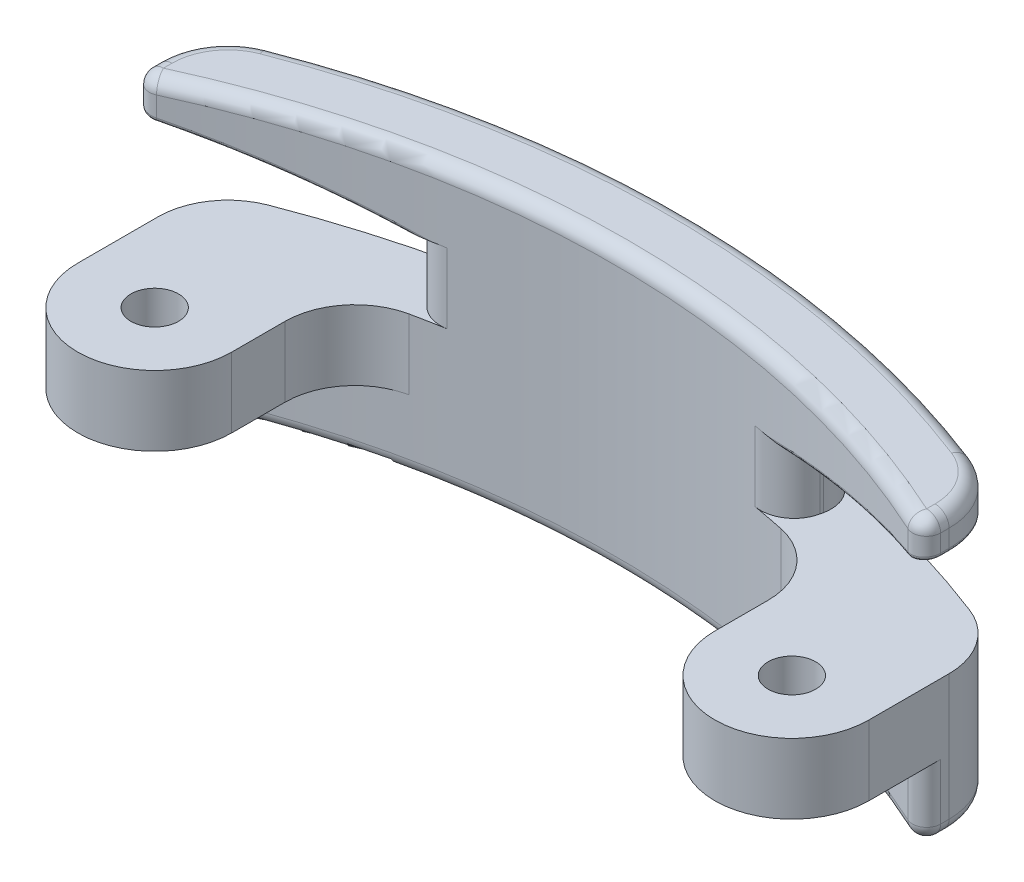
SolidWorks part; units mm, degrees
ref_plane "Front Plane" through (0, 0, 0) normal (0, 0, 1) x (1, 0, 0)
ref_plane "Top Plane" through (0, 0, 0) normal (0, 1, 0) x (1, 0, 0)
ref_plane "Right Plane" through (0, 0, 0) normal (1, 0, 0) x (0, 0, -1)
sketch "Sketch1" plane through (0, 0, 0) normal (0, 1, 0) x (1, 0, 0)
  line L0 (0, 0) -> (45.5, 0) construction
  line L1 (0, -54.3) -> (45.5, -54.3) construction
  line L2 (45.5, -54.3) -> (45.5, 0) construction
  line L3 (0, -54.3) -> (0, 0) construction
  line L4 (5.5, 0) -> (5.5, 3.7957)
  line L5 (40, 0) -> (40, 3.7957)
  line L6 (51, 0) -> (51, 5.7279)
  line L7 (-5.5, 0) -> (-5.5, 5.7279)
  line L8 (0.5, 0) -> (0.5, 11.4083) construction
  line L9 (45, 0) -> (45, 11.4083) construction
  line L10 (40, 0) -> (40, 7.7189) construction
  line L11 (5.5, 0) -> (5.5, 7.7189) construction
  circle A0 centre (0, 0) radius 1.7
  circle A1 centre (45.5, 0) radius 1.7
  circle A2 centre (0, 0) radius 5 construction
  circle A3 centre (45.5, 0) radius 5 construction
  arc A4 (-1.9321, 4.6116) -> (47.4321, 4.6116) centre (22.75, -54.3) cw construction
  arc A5 (9.4684, 8.6881) -> (36.0316, 8.6881) centre (22.75, -54.3) cw
  arc A6 (-5.5, 0) -> (5.5, 0) centre (0, 0) ccw
  arc A7 (40, 0) -> (51, 0) centre (45.5, 0) ccw
  arc A8 (-2.1253, 5.0728) -> (47.6253, 5.0728) centre (22.75, -54.3) cw construction
  arc A9 (-2.3059, 10.3904) -> (47.8059, 10.3904) centre (22.75, -54.3) cw
  arc A10 (0.5, 11.4083) -> (45, 11.4083) centre (22.75, -54.3) cw construction
  arc A11 (-2.3059, 10.3904) -> (-5.5, 5.7279) centre (-0.5, 5.7279) ccw
  arc A12 (47.8059, 10.3904) -> (51, 5.7279) centre (46, 5.7279) cw
  arc A13 (5.5, 7.7189) -> (40, 7.7189) centre (22.75, -54.3) cw construction
  arc A14 (40, 3.7957) -> (36.0316, 8.6881) centre (35, 3.7957) ccw
  arc A15 (5.5, 3.7957) -> (9.4684, 8.6881) centre (10.5, 3.7957) cw
  point P35 (40, 7.7189)
  dimension "D1" = 3.4
  dimension "D2" = 3.4
  dimension "D4" = 10
  dimension "D5" = 10
  dimension "D7" = 0.5
  dimension "D8" = 7.7189
  dimension "D11" = 5
  dimension "D3" = 45.5
  dimension "D6" = 54.3
  dimension "D10" = 5
extrude "Boss-Extrude1" add sketch "Sketch1" along normal blind 5
sketch "Sketch2" plane through (0, 5, 0) normal (0, 1, 0) x (1, 0, 0)
  line L0 (8.9821, 10.9943) -> (8.9408, 11.1901)
  line L1 (36.5179, 10.9943) -> (36.5592, 11.1901)
  arc A0 (11.7409, 9.1248) -> (33.7591, 9.1248) centre (22.75, -54.3) cw
  arc A1 (33.7591, 9.1248) -> (36.5179, 10.9943) centre (34.1695, 11.4895) ccw
  arc A2 (11.7409, 9.1248) -> (8.9821, 10.9943) centre (11.3305, 11.4895) cw
  arc A3 (36.0316, 8.6881) -> (9.4684, 8.6881) centre (22.75, -54.3) ccw construction
  arc A4 (47.8059, 10.3904) -> (-2.3059, 10.3904) centre (22.75, -54.3) ccw construction
  arc A5 (10.8785, 14.0499) -> (34.6215, 14.0499) centre (22.75, -54.3) cw
  arc A6 (36.5592, 11.1901) -> (34.6215, 14.0499) centre (34.2108, 11.6853) ccw
  arc A7 (8.9408, 11.1901) -> (10.8785, 14.0499) centre (11.2892, 11.6853) cw
  point P16 (36.0316, 8.6881)
  point P19 (9.4684, 8.6881)
  point P22 (37.0632, 13.5806)
  point P25 (8.4368, 13.5806)
  dimension "D1" = 2.4
extrude "Boss-Extrude2" add sketch "Sketch2" along normal blind 5
sketch "Sketch3" plane through (0, 5, 0) normal (0, 1, 0) x (1, 0, 0)
  line L0 (-5.5, 5.123) -> (-5.5, 5.7279)
  line L1 (51, 5.123) -> (51, 5.7279)
  arc A0 (-2.3059, 10.3904) -> (47.8059, 10.3904) centre (22.75, -54.3) cw
  arc A1 (34.6215, 14.0499) -> (10.8785, 14.0499) centre (22.75, -54.3) ccw construction
  arc A2 (-4.0832, 4.214) -> (49.5832, 4.214) centre (22.75, -54.3) cw
  arc A3 (33.7591, 9.1248) -> (11.7409, 9.1248) centre (22.75, -54.3) ccw construction
  arc A4 (47.8059, 10.3904) -> (51, 5.7279) centre (46, 5.7279) cw
  arc A5 (-2.3059, 10.3904) -> (-5.5, 5.7279) centre (-0.5, 5.7279) ccw
  arc A6 (49.5832, 4.214) -> (51, 5.123) centre (50, 5.123) ccw
  arc A7 (-4.0832, 4.214) -> (-5.5, 5.123) centre (-4.5, 5.123) cw
  point P2 (51, 9.0607)
  point P10 (-5.5, 9.0607)
  point P17 (51, 3.5433)
  point P23 (-5.5, 3.5433)
  dimension "D1" = 5.5174
  dimension "D3" = 5
  dimension "D4" = 1
  dimension "D2" = 5.5174
extrude "Boss-Extrude3" add sketch "Sketch3" along normal blind 5 from offset 5 separate body
mirror "Mirror1" about plane through (-0.5, 5, -5.7279) normal (0, 1, 0) of "Boss-Extrude3"
ref_plane "Plane2" through (0, 0, -10.3904) normal (0, 0, 1) x (1, 0, 0)
sketch "Sketch6" plane through (0, 0, -10.3904) normal (0, 0, 1) x (1, 0, 0)
  line L0 (8.9821, 10) -> (-5.5, 12.5)
  line L1 (-5.5, 15) -> (-5.5, 10) construction
  line L2 (-5.5, 12.5) -> (-5.5, 10)
  line L3 (-5.5, 10) -> (8.9821, 10)
  line L4 (36.5592, 10) -> (51, 12.5)
  line L5 (51, 15) -> (51, 10) construction
  line L6 (51, 12.5) -> (51, 10)
  line L7 (51, 10) -> (36.5592, 10)
extrude "Cut-Extrude2" cut sketch "Sketch6" against normal blind 5 and the other way blind 10
fillet "Fillet1" radius 1 16 edges at (50.1249, 15, -8.5537) (51, 15, -5.4254) (50.54, 15, -4.2813) (22.75, 15, -10.0732) (-5.04, 15, -4.2813) (-5.5, 15, -5.4254) (-4.6249, 15, -8.5537) (50.1249, -5, -8.5537) (51, -5, -5.4254) (50.54, -5, -4.2813) (22.75, -5, -10.0732) (-5.04, -5, -4.2813) (-5.5, -5, -5.4254) (-4.6249, -5, -8.5537) (22.75, 15, -15.0732) (22.75, -5, -15.0732)
fillet "Fillet2" radius 0.3 10 edges at (2.3322, 11.1479, -6.7493) (-5.04, 12.4206, -4.2813) (-5.5, 12.5, -5.4254) (3.268, 10.9864, -12.2815) (42.2522, 10.9856, -12.2755) (43.1878, 11.1475, -6.7426) (50.54, 12.4204, -4.2813) (51, 12.5, -5.4254) (-4.6249, 12.3489, -8.5537) (50.1249, 12.3485, -8.5537)
ref_plane "Plane3" through (0, 0, -14.0499) normal (0, 0, -1) x (-1, 0, 0)
sketch "Sketch7" plane through (0, 0, -14.0499) normal (0, 0, -1) x (-1, 0, 0)
  line L0 (-34.6215, 8.2308) -> (-10.8785, 8.2308) construction
  line L3 (-10.8785, 10) -> (-10.8785, 5) construction
  text T0 "4N7v2" font "Century Gothic" height 5
  point P3 (-10.8785, 7.5)
  point P4 (-10.8785, 8.2308)
extrude "Cut-Extrude3" cut sketch "Sketch7" along normal blind 5 and the other way blind 2
